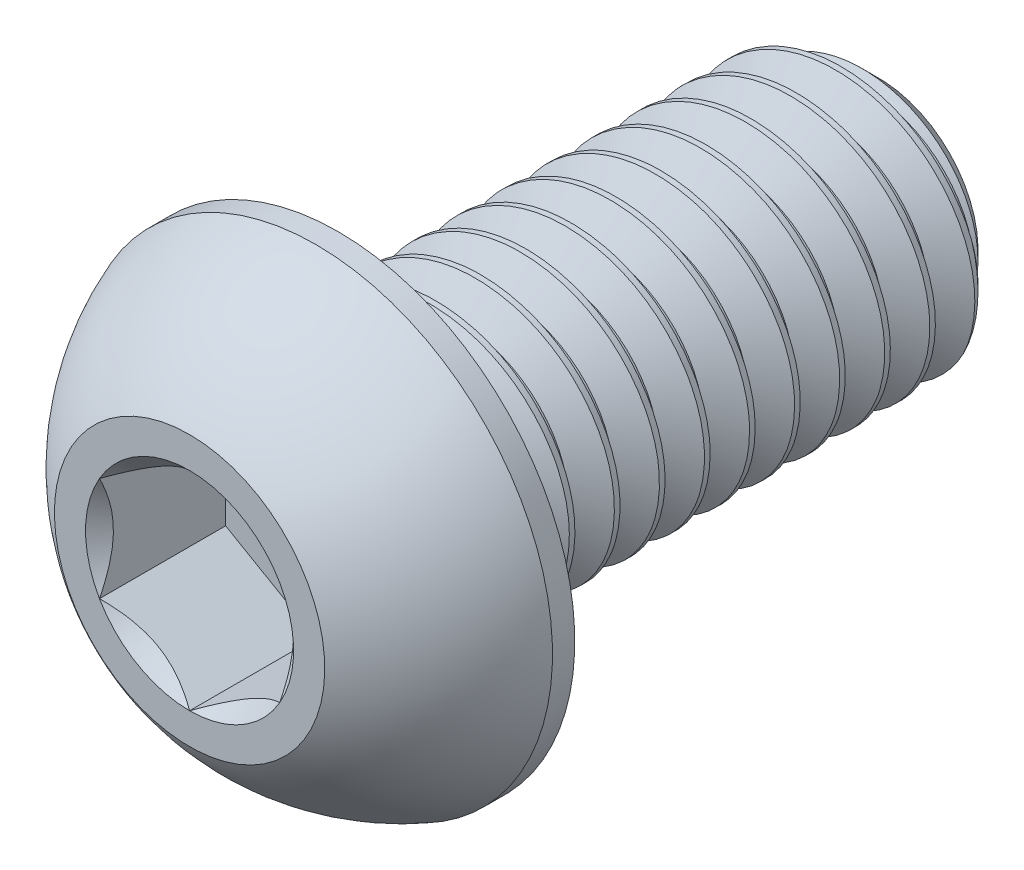
SolidWorks part; units mm, degrees
material "Alloy Steel"
ref_plane "Front Plane" through (0, 0, 0) normal (0, 0, 1) x (1, 0, 0)
ref_plane "Top Plane" through (0, 0, 0) normal (0, 1, 0) x (1, 0, 0)
ref_plane "Right Plane" through (0, 0, 0) normal (1, 0, 0) x (0, 0, -1)
sketch "Sketch1" plane through (0, 0, 0) normal (1, 0, 0) x (0, 0, -1)
  line L0 (-7.65, 0) -> (7.65, 0) construction
  line L1 (-4.35, 5.25) -> (-4.35, -5.25) construction
  line L2 (7.65, 3) -> (7.65, -3) construction
  line L3 (7.5875, 3.1083) -> (8.0875, 2.2422) construction
  line L4 (8.0875, 2.2422) -> (8.5875, 3.1083) construction
  line L5 (8.5875, 3.1083) -> (7.5875, 3.1083) construction
  line L6 (7.65, 3) -> (8.525, 3) construction
  line L7 (8.0875, 3.1083) -> (8.0875, 3) construction
  line L8 (8.0875, 3) -> (8.0875, 2.3505) construction
  line L9 (8.0875, 2.3505) -> (8.0875, 2.2422) construction
  line L10 (8.025, 2.3505) -> (8.15, 2.3505)
  line L11 (7.6188, 3.0541) -> (8.5563, 3.0541)
  line L12 (8.15, 2.3505) -> (8.5563, 3.0541)
  line L13 (8.025, 2.3505) -> (7.6188, 3.0541)
  line L14 (-7.65, 2) -> (-7.65, -2) construction
  line L15 (7.65, 3) -> (-4.35, 3) construction
  point P3 (-4.35, 0)
  point P6 (-4.85, 0)
  point P21 (8.0875, 3.0541)
  point P24 (-4.845, 5.25)
  point P25 (5.15, -3)
  point P26 (-7.65, 3)
  dimension "Head Height" = 3.3
  dimension "Length" = 12
  dimension "Head Dia" = 10.5
  dimension "Thread Dia" = 6
  dimension "Pitch" = 1
  dimension "D2" = 0.125
  dimension "Drive Size" = 4
  dimension "D1" = 2.8
  dimension "D3" = 0.495
  dimension "D4" = 2.5
sketch "Sketch2" plane through (0, 0, 0) normal (1, 0, 0) x (0, 0, -1)
  line L0 (-7.65, 0) -> (7.65, 0)
  line L1 (7.65, 0) -> (7.65, 2.2)
  line L2 (7.65, 3) -> (7.65, -3) construction
  line L3 (7.65, 2.2) -> (6.85, 3)
  line L4 (6.85, 3) -> (-4.35, 3)
  line L5 (-4.35, 5.25) -> (-4.35, -5.25) construction
  line L6 (-4.35, 3) -> (-4.35, 5.25)
  line L7 (-4.35, 5.25) -> (-4.845, 5.25)
  line L8 (7.65, 3) -> (8.525, 3) construction
  line L9 (-7.65, 0) -> (-7.65, 3)
  arc A0 (-7.65, 3) -> (-4.845, 5.25) centre (-2.9387, 0) cw
  dimension "D1" = 0.8
  dimension "D2" = 45
revolve "Revolve1" add sketch "Sketch2" angle 360 about L0
sketch "Sketch3" plane through (0, 0, 7.65) normal (0, 0, 1) x (1, 0, 0)
  line L1 (0, 2.3094) -> (-2, 1.1547)
  line L2 (-2, 1.1547) -> (-2, -1.1547)
  line L3 (-2, -1.1547) -> (0, -2.3094)
  line L4 (0, -2.3094) -> (2, -1.1547)
  line L5 (2, -1.1547) -> (2, 1.1547)
  line L6 (2, 1.1547) -> (0, 2.3094)
  circle A0 centre (0, 0) radius 2 construction
  dimension "D1" = 4
extrude "Cut-Extrude1" cut sketch "Sketch3" against normal up to vertex (2.8 mm away) up to point (0, 0, 4.85)
sketch "Sketch4" plane through (0, 0, 7.65) normal (0, 0, 1) x (1, 0, 0)
  circle A0 centre (0, 0) radius 2.3094
extrude "Cut-Extrude2" cut sketch "Sketch4" against normal blind 10 draft 45
split "Split1" bodies to split 106 resulting bodies 107 108 split by face at (0, -5.25, 4.35)
sketch "Sketch5" plane through (0, 0, -7.65) normal (0, 0, -1) x (-1, 0, 0)
  circle A0 centre (0, 0) radius 3 construction
  circle A1 centre (0, 0) radius 3
curve "Helix/Spiral1" pitch 1 height 13 radius 3 centre (0, 0, -7.65) axis (0, 0, 1) start towards (0, 1, 0)
sketch "Sketch6" plane through (0, 0, 0) normal (1, 0, 0) x (0, 0, -1)
  line L0 (8.025, 2.3505) -> (8.15, 2.3505) construction
  line L1 (8.025, 2.3505) -> (7.6188, 3.0541) construction
  line L2 (7.6188, 3.0541) -> (8.5563, 3.0541) construction
  line L3 (8.15, 2.3505) -> (8.5563, 3.0541) construction
  line L4 (8.025, 2.3505) -> (8.15, 2.3505)
  line L5 (8.025, 2.3505) -> (7.6188, 3.0541)
  line L6 (7.6188, 3.0541) -> (8.5563, 3.0541)
  line L7 (8.15, 2.3505) -> (8.5563, 3.0541)
sweep "Cut-Sweep1" cut profiles "Sketch6" path "Helix/Spiral1" align with end faces yes
sketch "Sketch7" plane through (0, 0, 4.35) normal (0, 0, -1) x (-1, 0, 0)
  circle A1 centre (0, 0) radius 3
  circle A2 centre (0, 0) radius 3
  dimension "D1" = 0
extrude "Boss-Extrude1" add sketch "Sketch7" along normal blind 10 draft 30
equation "\"D2@Sketch1\" = \"Pitch@Sketch1\" / 8"
equation "\"D1@Sketch1\"=\"Drive Size@Sketch1\"*.7"
equation "\"D3@Sketch1\"=\"Head Height@Sketch1\"*.15"
equation "\"D1@Sketch2\"=\"Pitch@Sketch1\"*.8"
equation "\"D1@Sketch3\"=\"Drive Size@Sketch1\""
equation "\"D4@Helix/Spiral1\"=\"Pitch@Sketch1\""
equation "\"D3@Helix/Spiral1\"=\"Length@Sketch1\"+\"Pitch@Sketch1\""
equation "\"D4@Sketch1\"=\"Pitch@Sketch1\"*2.5"
